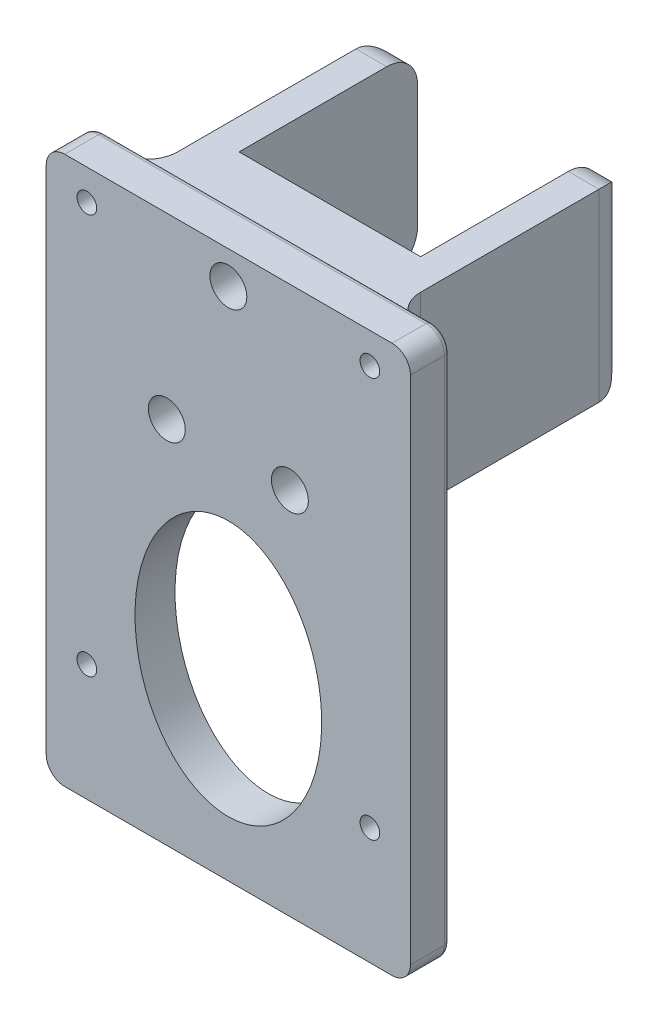
SolidWorks part; units mm, degrees
ref_plane "前视基准面" through (0, 0, 0) normal (0, 0, 1) x (1, 0, 0)
ref_plane "上视基准面" through (0, 0, 0) normal (0, 1, 0) x (1, 0, 0)
ref_plane "右视基准面" through (0, 0, 0) normal (1, 0, 0) x (0, 0, -1)
sketch "草图1" plane through (0, 0, 0) normal (0, 0, 1) x (1, 0, 0)
  line L5 (-23, 32.5) -> (23, 32.5) construction
  line L6 (-23, 32.5) -> (-23, -32.5) construction
  line L7 (-23, -32.5) -> (23, -32.5) construction
  line L8 (23, 32.5) -> (23, -32.5) construction
  line L9 (-23, 32.5) -> (23, -32.5) construction
  line L10 (-23, -32.5) -> (23, 32.5) construction
  line L11 (-29.6, 37.5) -> (29.6, 37.5)
  line L12 (-29.6, 37.5) -> (-29.6, -51.5)
  line L13 (-29.6, -51.5) -> (29.6, -51.5)
  line L14 (29.6, 37.5) -> (29.6, -51.5)
  line L15 (-29.6, 37.5) -> (29.6, -51.5) construction
  line L16 (-29.6, -51.5) -> (29.6, 37.5) construction
  circle A4 centre (-23, -32.5) radius 1.6
  circle A5 centre (23, -32.5) radius 1.6
  circle A6 centre (23, 32.5) radius 1.6
  circle A7 centre (-23, 32.5) radius 1.6
  point P0 (0, 0)
  point P1 (0, 0)
  point P11 (0, -7)
  dimension "D1" = 65
  dimension "D2" = 46
  dimension "D3" = 3.2
  dimension "D4" = 3.2
  dimension "D5" = 3.2
  dimension "D6" = 3.2
  dimension "D7" = 5
  dimension "D8" = 6.6
  dimension "D9" = 59.2
  dimension "D10" = 89
extrude "凸台-拉伸1" add sketch "草图1" along normal blind 6.5
sketch "草图2" plane through (0, 0, 0) normal (0, 0, -1) x (-1, 0, 0)
  line L0 (0, 37.5) -> (0, -51.5) construction
  line L1 (-29.6, 37.5) -> (29.6, 37.5) construction
  line L2 (29.6, -51.5) -> (-29.6, -51.5) construction
  line L4 (-14.75, 5.5) -> (14.75, 5.5)
  line L5 (-14.75, 5.5) -> (-14.75, 35.5)
  line L6 (-14.75, 35.5) -> (14.75, 35.5)
  line L7 (14.75, 5.5) -> (14.75, 35.5)
  line L8 (-14.75, 5.5) -> (14.75, 35.5) construction
  line L9 (-14.75, 35.5) -> (14.75, 5.5) construction
  point P6 (0, 20.5)
  dimension "D1" = 30
  dimension "D2" = 29.5
  dimension "D3" = 2
extrude "凸台-拉伸2" add sketch "草图2" along normal blind 10
sketch "草图3" plane through (0, 0, 0) normal (0, 0, -1) x (-1, 0, 0)
  line L1 (14.75, 35.5) -> (19.75, 35.5)
  line L2 (14.75, 35.5) -> (14.75, 5.5)
  line L3 (14.75, 5.5) -> (19.75, 5.5)
  line L4 (19.75, 35.5) -> (19.75, 5.5)
  line L5 (-14.75, 35.5) -> (-19.75, 35.5)
  line L6 (-14.75, 35.5) -> (-14.75, 5.5)
  line L7 (-14.75, 5.5) -> (-19.75, 5.5)
  line L8 (-19.75, 35.5) -> (-19.75, 5.5)
  dimension "D1" = 5
  dimension "D2" = 5
extrude "凸台-拉伸3" add sketch "草图3" along normal blind 39
sketch "草图4" plane through (0, 0, 0) normal (0, 0, -1) x (-1, 0, 0)
  circle A0 centre (23, -32.5) radius 2.75
  circle A1 centre (-23, -32.5) radius 2.75
  circle A2 centre (23, 32.5) radius 2.75
  circle A3 centre (-23, 32.5) radius 2.75
  dimension "D1" = 5.5
  dimension "D2" = 5.5
  dimension "D3" = 5.5
  dimension "D4" = 5.5
extrude "切除-拉伸1" cut sketch "草图4" against normal blind 3.2
sketch "草图5" plane through (0, 0, -10) normal (0, 0, -1) x (-1, 0, 0)
  line L0 (0, 5.5) -> (0, 35.5) construction
  line L1 (-14.75, 5.5) -> (14.75, 5.5) construction
  line L2 (14.75, 35.5) -> (-14.75, 35.5) construction
  line L3 (10, 8.5) -> (-10, 8.5) construction
  line L4 (19.75, 35.5) -> (-19.75, 35.5) construction
  circle A0 centre (0, 32.2) radius 1.6
  circle A1 centre (10, 8.5) radius 1.6
  circle A2 centre (-10, 8.5) radius 1.6
  point P2 (0, 8.5)
  dimension "D1" = 3.2
  dimension "D2" = 3.2
  dimension "D3" = 3.2
  dimension "D4" = 20
  dimension "D5" = 23.7
  dimension "D6" = 3.3
extrude "切除-拉伸2" cut sketch "草图5" against normal blind 100 and the other way blind 100
sketch "草图6" plane through (0, 0, 6.5) normal (0, 0, 1) x (1, 0, 0)
  circle A0 centre (10, 8.5) radius 3
  circle A1 centre (-10, 8.5) radius 3
  circle A2 centre (0, 32.2) radius 3
  dimension "D1" = 6
  dimension "D2" = 6
  dimension "D3" = 6
extrude "切除-拉伸3" cut sketch "草图6" against normal blind 5.5
fillet "圆角1" radius 3 4 edges at (-29.6, 37.5, 3.25) (29.6, 37.5, 3.25) (29.6, -51.5, 3.25) (-29.6, -51.5, 3.25)
fillet "圆角2" radius 5 3 edges at (0, 5.5, 0) (-19.75, 20.5, 0) (19.75, 20.5, 0)
fillet "圆角5" radius 1 8 edges at (0, 37.5, 0) (28.7213, -50.6213, 0) (29.6, -7, 0) (-28.7213, -50.6213, 0) (-29.6, -7, 0) (0, -51.5, 0) (28.7213, 36.6213, 0) (-28.7213, 36.6213, 0)
fillet "圆角6" radius 5 6 edges at (-17.25, 35.5, -39) (17.25, 35.5, -39) (-19.75, 20.5, -39) (-17.25, 5.5, -39) (17.25, 5.5, -39) (19.75, 20.5, -39)
sketch "草图7" plane through (0, 0, 6.5) normal (0, 0, 1) x (1, 0, 0)
  ellipse E0 centre (0, -21.6267) end of major axis (0, -42.4507) minor radius 15.171
extrude "切除-拉伸4" cut sketch "草图7" against normal blind 10
